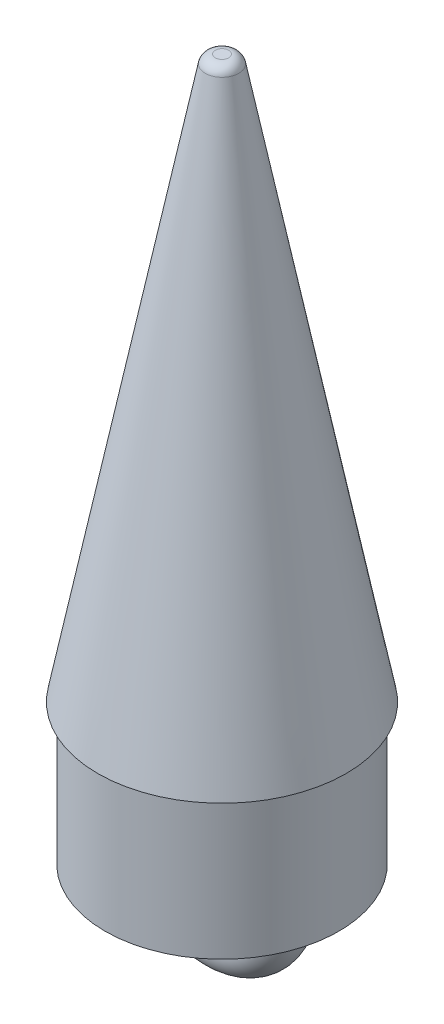
SolidWorks part; units mm, degrees
ref_plane "Front Plane" through (0, 0, 0) normal (0, 0, 1) x (1, 0, 0)
ref_plane "Top Plane" through (0, 0, 0) normal (0, 1, 0) x (1, 0, 0)
ref_plane "Right Plane" through (0, 0, 0) normal (1, 0, 0) x (0, 0, -1)
sketch "Sketch1" plane through (0, 0, 0) normal (0, 1, 0) x (1, 0, 0)
  circle A0 centre (0, 0) radius 31.75
  dimension "D1" = 63.5
extrude "Boss-Extrude1" add sketch "Sketch1" along normal blind 38.1 contours A0
sketch "Sketch2" plane through (0, 38.1, 0) normal (0, 1, 0) x (1, 0, 0)
  circle A0 centre (0, 0) radius 33.7344
  dimension "D1" = 67.4688
extrude "Boss-Extrude2" add sketch "Sketch2" along normal blind 152.4 draft 11
fillet "Fillet1" radius 2.794 1 edges at (0, 190.5, 4.1108)
shell "Shell3" thickness 1.27
sketch "Sketch4" plane through (0, 0, 0) normal (0, -1, 0) x (1, 0, 0)
  line L0 (0, 0) -> (0, -8.7445) construction
  circle A0 centre (-17.0804, 0) radius 6.35
  dimension "D1" = 12.7
revolve "Revolve1" add sketch "Sketch4" angle 180 about L0 reverse direction yes
sketch "Sketch5" plane through (0, 0, 0) normal (0, -1, 0) x (1, 0, 0)
  circle A0 centre (0, 0) radius 31.75
extrude "Boss-Extrude3" add sketch "Sketch5" against normal blind 6.35
